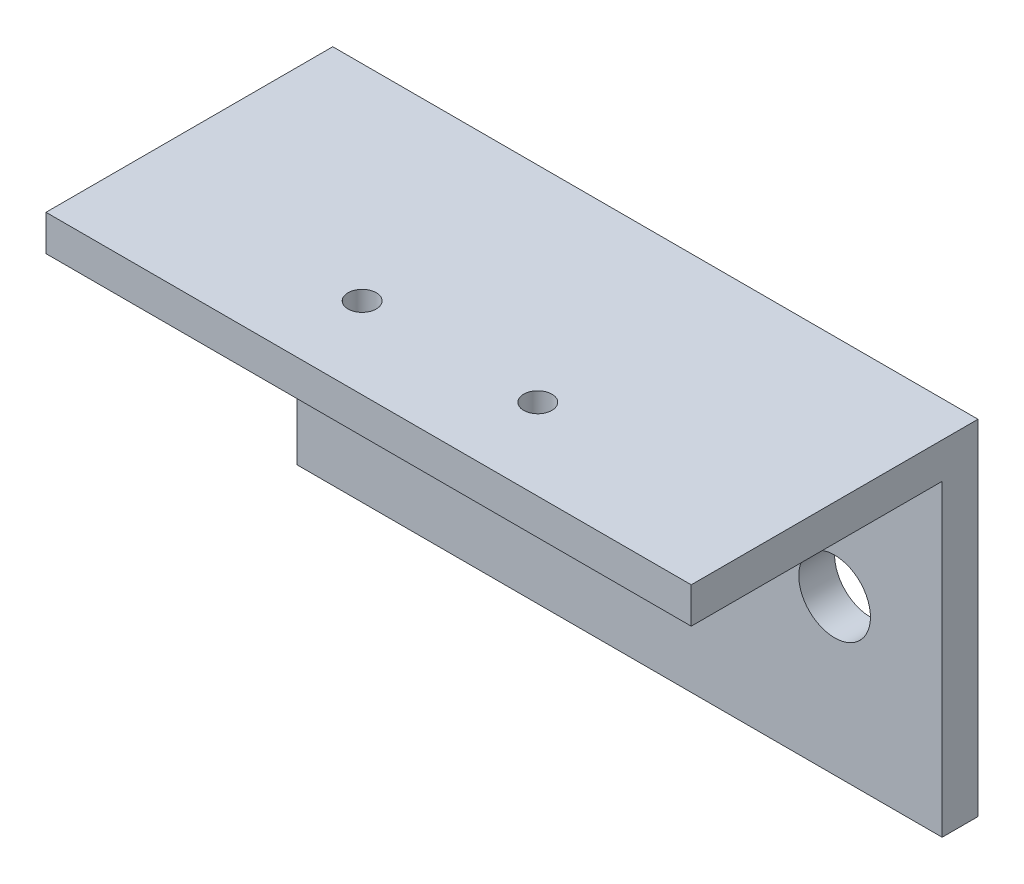
SolidWorks part; units mm, degrees
material "6061-T6 (SS)"
ref_plane "Front Plane" through (0, 0, 0) normal (0, 0, 1) x (1, 0, 0)
ref_plane "Top Plane" through (0, 0, 0) normal (0, 1, 0) x (1, 0, 0)
ref_plane "Right Plane" through (0, 0, 0) normal (1, 0, 0) x (0, 0, -1)
sketch "Sketch3" plane through (0, 0, 0) normal (0, 0, 1) x (1, 0, 0)
  line L1 (0, 0) -> (57.15, 0)
  line L2 (0, 0) -> (0, 30.48)
  line L3 (0, 30.48) -> (57.15, 30.48)
  line L4 (57.15, 0) -> (57.15, 30.48)
  dimension "D1" = 57.15
  dimension "D2" = 30.48
extrude "Boss-Extrude2" add sketch "Sketch3" along normal blind 3.175
sketch "Sketch4" plane through (0, 0, 3.175) normal (0, 0, 1) x (1, 0, 0)
  line L0 (57.15, 0) -> (57.15, 30.48) construction
  line L1 (0, 30.48) -> (57.15, 30.48)
  line L2 (0, 30.48) -> (0, 27.305)
  line L3 (0, 27.305) -> (57.15, 27.305)
  line L4 (57.15, 30.48) -> (57.15, 27.305)
  dimension "D1" = 3.175
extrude "Boss-Extrude3" add sketch "Sketch4" along normal offset from surface (22.225 mm away) 25.4 up to face at (28.575, 15.24, 0)
sketch "Sketch6" plane through (0, 30.48, 0) normal (0, 1, 0) x (1, 0, 0)
  line L0 (20.7968, -18.194) -> (36.3532, -18.194) construction
  line L2 (57.15, 0) -> (0, 0) construction
  line L4 (0, -25.4) -> (57.15, -25.4) construction
  line L5 (28.575, -25.4) -> (28.575, -18.194) construction
  line L6 (36.3532, -2.6377) -> (36.3532, -18.194) construction
  circle A0 centre (36.3532, -18.194) radius 1.25
  circle A1 centre (20.7968, -18.194) radius 1.25
  point P9 (28.575, 0)
  dimension "D3" = 2.5
  dimension "D1" = 18.194
  dimension "D2" = 22
extrude "Cut-Extrude1" cut sketch "Sketch6" against normal blind 3.175
sketch "Sketch7" plane through (0, 0, 3.175) normal (0, 0, 1) x (1, 0, 0)
  line L0 (-27.648, 54.48) -> (77.5251, 54.48) construction
  line L1 (0, 0) -> (57.15, 0) construction
  line L2 (9.525, 13.713) -> (47.625, 13.713) construction
  line L3 (0, 30.48) -> (57.15, 30.48) construction
  line L4 (28.575, 0) -> (28.575, 13.713) construction
  circle A0 centre (47.625, 13.713) radius 3.175
  circle A1 centre (9.525, 13.713) radius 3.175
  dimension "D3" = 6.35
  dimension "D1" = 81.534
  dimension "D2" = 38.1
  dimension "D4" = 24
extrude "Cut-Extrude2" cut sketch "Sketch7" against normal blind 3.175 contours A1 | A0
